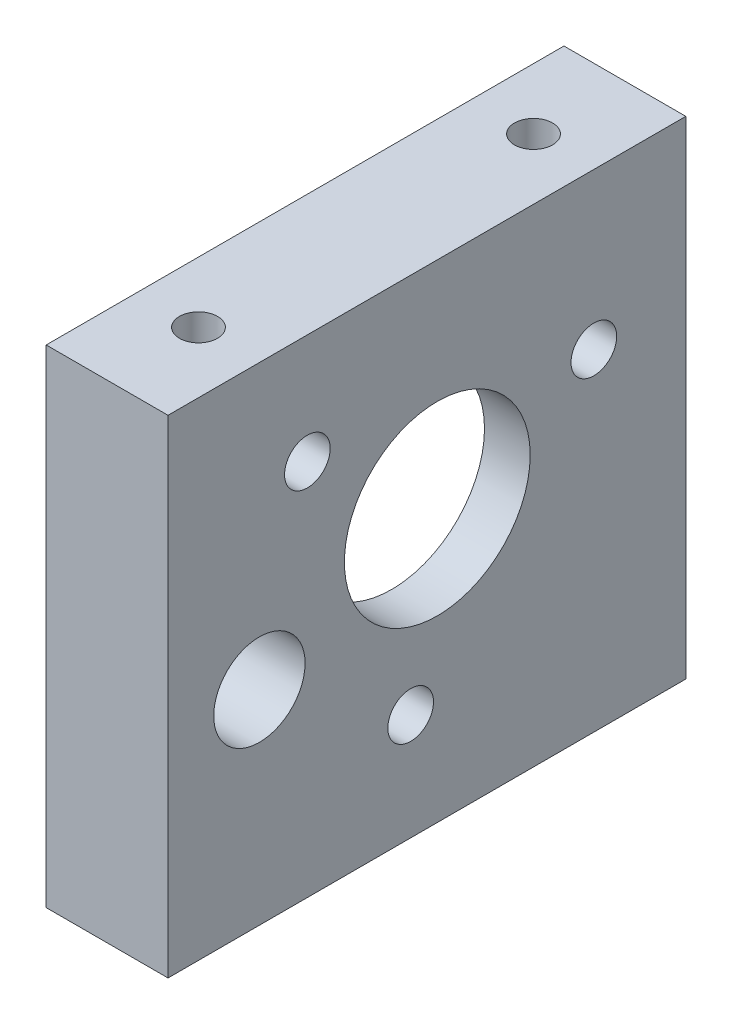
SolidWorks part; units mm, degrees
ref_plane "Front Plane" through (0, 0, 0) normal (0, 0, 1) x (1, 0, 0)
ref_plane "Top Plane" through (0, 0, 0) normal (0, 1, 0) x (1, 0, 0)
ref_plane "Right Plane" through (0, 0, 0) normal (1, 0, 0) x (0, 0, -1)
sketch "Sketch1" plane through (0, 0, 0) normal (1, 0, 0) x (0, 0, -1)
  line L1 (0, 0) -> (34, 0)
  line L2 (0, 0) -> (0, 32)
  line L3 (0, 32) -> (34, 32)
  line L4 (34, 0) -> (34, 32)
  dimension "D1" = 32
  dimension "D2" = 34
extrude "Boss-Extrude1" add sketch "Sketch1" along normal blind 8
sketch "Sketch2" plane through (8, 0, 0) normal (1, 0, 0) x (0, 0, -1)
  line L0 (27.9604, 21.766) -> (6, 13.4) construction
  line L1 (0, 0) -> (34, 0) construction
  line L3 (0, 0) -> (34, 0) construction
  line L5 (0, 32) -> (0, 0) construction
  circle A0 centre (17.6811, 17.85) radius 6.1
  circle A1 centre (6, 13.4) radius 3
  circle A2 centre (27.9604, 21.766) radius 1.5
  dimension "D2" = 12.2
  dimension "D3" = 3
  dimension "D6" = 6
  dimension "D1" = 6
  dimension "D4" = 13.4
  dimension "D5" = 11
  dimension "D7" = 17.85
  dimension "D8" = 12.5
extrude "Cut-Extrude1" cut sketch "Sketch2" against normal up to next
pattern_circular "CirPattern1" count 3 over 360 about axis through (8, 17.85, -17.6811) along (1, 0, 0) of face at (0, 21.766, -26.4604)
sketch "Sketch3" plane through (0, 0, 0) normal (1, 0, 0) x (0, 0, -1)
  line L0 (32, 25) -> (32, 7)
  line L1 (29, 4) -> (15, 4)
  line L2 (12, 7) -> (12, 13.4)
  line L3 (6, 21.8853) -> (6, 25)
  line L4 (9, 28) -> (29, 28)
  line L5 (34, 0) -> (34, 32) construction
  line L6 (0, 0) -> (34, 0) construction
  line L7 (34, 32) -> (0, 32) construction
  line L8 (0, 32) -> (0, 0) construction
  arc A0 (12, 13.4) -> (8, 19.0569) centre (6, 13.4) ccw
  arc A1 (8, 19.0569) -> (6, 21.8853) centre (9, 21.8853) cw
  arc A2 (15, 4) -> (12, 7) centre (15, 7) cw
  arc A3 (32, 7) -> (29, 4) centre (29, 7) cw
  arc A4 (32, 25) -> (29, 28) centre (29, 25) ccw
  arc A5 (6, 25) -> (9, 28) centre (9, 25) cw
  dimension "D4" = 3
  dimension "D5" = 3
  dimension "D1" = 2
  dimension "D2" = 4
  dimension "D3" = 4
  dimension "D6" = 6
  dimension "D7" = 12
extrude "Cut-Extrude2" cut sketch "Sketch3" along normal blind 5
hole_wizard "Tap Drill for M3x0.5 Tap1" positions "Sketch5" profile "Sketch4" hole size "M3x0.5" standard "ANSI Metric"
sketch "Sketch5" plane through (0, 32, 0) normal (0, 1, 0) x (-1, 0, 0)
  line L0 (0, -34) -> (0, 0) construction
  line L1 (-8, 0) -> (0, 0) construction
  line L2 (-8, -34) -> (0, -34) construction
  point P0 (-4, -6)
  point P2 (-4, -28)
  dimension "D1" = 4
  dimension "D2" = 6
  dimension "D3" = 6
sketch "Sketch4" plane through (4, 32, -6) normal (1, 0, 0) x (0, 0, 1)
  line L0 (0, 0) -> (0, 3.7511)
  line L1 (0, 3.7511) -> (1.25, 3)
  line L2 (1.25, 3) -> (1.25, 0)
  line L5 (1.25, 0) -> (0, 0)
  line L10 (0, 3.7511) -> (-1.25, 3) construction
  line L11 (0, -6.35) -> (0, 107.95) construction
  dimension "Hole Dia." = 2.5
  dimension "Hole Depth" = 3
  dimension "Drill Angle" = 118
hole_wizard "Tap Drill for M3x0.5 Tap2" positions "Sketch7" profile "Sketch6" hole size "M3x0.5" standard "ANSI Metric"
sketch "Sketch7" plane through (0, 0, 0) normal (0, -1, 0) x (1, 0, 0)
  line L0 (8, 0) -> (0, 0) construction
  line L1 (8, -34) -> (0, -34) construction
  line L2 (8, 0) -> (8, -34) construction
  point P0 (4, -6)
  point P2 (4, -28)
  dimension "D1" = 6
  dimension "D2" = 6
  dimension "D3" = 4
sketch "Sketch6" plane through (4, 0, -6) normal (1, 0, 0) x (0, 0, -1)
  line L0 (0, 0) -> (0, 3.7511)
  line L1 (0, 3.7511) -> (1.25, 3)
  line L2 (1.25, 3) -> (1.25, 0)
  line L5 (1.25, 0) -> (0, 0)
  line L10 (0, 3.7511) -> (-1.25, 3) construction
  line L11 (0, -6.35) -> (0, 107.95) construction
  dimension "Hole Dia." = 2.5
  dimension "Hole Depth" = 3
  dimension "Drill Angle" = 118
